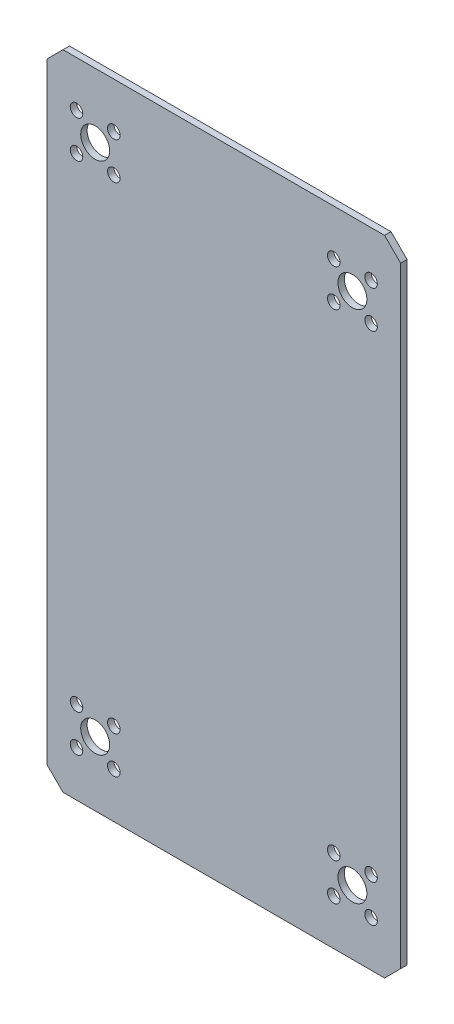
SolidWorks part; units mm, degrees
material "201 Annealed Stainless Steel (SS)"
ref_plane "Front Plane" through (0, 0, 0) normal (0, 0, 1) x (1, 0, 0)
ref_plane "Top Plane" through (0, 0, 0) normal (0, 1, 0) x (1, 0, 0)
ref_plane "Right Plane" through (0, 0, 0) normal (1, 0, 0) x (0, 0, -1)
sketch "Sketch1" plane through (0, 0, 0) normal (0, 0, 1) x (1, 0, 0)
  line L1 (-55, -100) -> (55, -100)
  line L2 (-55, -100) -> (-55, 100)
  line L3 (-55, 100) -> (55, 100)
  line L4 (55, -100) -> (55, 100)
  line L5 (-55, -100) -> (55, 100) construction
  line L6 (-55, 100) -> (55, -100) construction
  point P0 (0, 0)
  dimension "D1" = 110
  dimension "D2" = 200
extrude "Boss-Extrude1" add sketch "Sketch1" along normal blind 2
sketch "Sketch2" [suppressed] plane through (0, 0, 0) normal (0, 0, -1) x (-1, 0, 0)
  line L0 (61, 200) -> (61, -200) construction
  line L1 (-61, 314.7216) -> (-204.3993, 314.7216)
  line L2 (-61, 314.7216) -> (-61, -251.9618)
  line L3 (-61, -251.9618) -> (-204.3993, -251.9618)
  line L4 (-204.3993, 314.7216) -> (-204.3993, -251.9618)
  line L6 (61, 279.3211) -> (244.4765, 279.3211)
  line L7 (61, 279.3211) -> (61, -295.1839)
  line L8 (61, -295.1839) -> (244.4765, -295.1839)
  line L9 (244.4765, 279.3211) -> (244.4765, -295.1839)
  line L10 (-61, -200) -> (-61, -140) construction
extrude "Cut-Extrude1" [suppressed] cut sketch "Sketch2" against normal through all
sketch "Sketch3" [suppressed] plane through (49, 0, 0) normal (1, 0, 0) x (0, 0, -1)
  circle A0 centre (-6.722, 55.3681) radius 5.3835
surface "Surface-Extrude1" [suppressed] sketch "Sketch3"
sketch "Sketch4" [suppressed] plane through (-49, 0, 0) normal (-1, 0, 0) x (0, 0, 1)
  line L1 (2, 80) -> (0, 80) construction
  line L2 (0, -80) -> (0, 80) construction
  point P0 (7.5, 76)
  dimension "D1" = 4
  dimension "D2" = 7.5
ref_axis "Axis1" [suppressed] through (-49, 76, 7.5) along (1, 0, 0)
sketch "Sketch5" [suppressed] plane through (0, 0, 0) normal (0, 0, -1) x (-1, 0, 0)
  line L0 (49, 80) -> (49, -80) construction
  line L1 (-49, 80) -> (49, 80)
  line L2 (-49, 80) -> (-49, 60.2594)
  line L3 (-49, 60.2594) -> (49, 60.2594)
  line L4 (49, 80) -> (49, 60.2594)
extrude "Cut-Extrude2" [suppressed] cut sketch "Sketch5" against normal blind 3
sketch "Sketch6" plane through (0, 0, 2) normal (0, 0, 1) x (1, 0, 0)
  line L0 (0, 0) -> (103.2002, 0) construction
  line L1 (-40, 80) -> (-40, 108.3319) construction
  line L2 (-40, 80) -> (-27.987, 80) construction
  line L3 (0, 0) -> (0, 138.3235) construction
  line L4 (40, 80) -> (27.987, 80) construction
  line L5 (40, 80) -> (40, 108.3319) construction
  line L6 (40, -80) -> (40, -108.3319) construction
  line L7 (40, -80) -> (27.987, -80) construction
  line L8 (-40, -80) -> (-27.987, -80) construction
  line L9 (-40, -80) -> (-40, -108.3319) construction
  circle A0 centre (-40, 80) radius 4.5
  circle A2 centre (-45.8, 85.8) radius 1.95
  circle A3 centre (-45.8, 74.2) radius 1.95
  circle A4 centre (-34.2, 74.2) radius 1.95
  circle A5 centre (-34.2, 85.8) radius 1.95
  circle A6 centre (34.2, 85.8) radius 1.95
  circle A7 centre (34.2, 74.2) radius 1.95
  circle A8 centre (45.8, 74.2) radius 1.95
  circle A9 centre (45.8, 85.8) radius 1.95
  circle A10 centre (40, 80) radius 4.5
  circle A11 centre (40, -80) radius 4.5
  circle A12 centre (45.8, -85.8) radius 1.95
  circle A13 centre (45.8, -74.2) radius 1.95
  circle A14 centre (34.2, -74.2) radius 1.95
  circle A15 centre (34.2, -85.8) radius 1.95
  circle A16 centre (-34.2, -85.8) radius 1.95
  circle A17 centre (-34.2, -74.2) radius 1.95
  circle A18 centre (-45.8, -74.2) radius 1.95
  circle A19 centre (-45.8, -85.8) radius 1.95
  circle A20 centre (-40, -80) radius 4.5
  circle A21 centre (-40, 80) radius 5.1 construction
  point P52 (47.4466, 77.7566)
  point P53 (0, 0)
  point P54 (48.5598, 78.7073)
  dimension "D1" = 9
  dimension "D3" = 3.9
extrude "Leandut_holes" cut sketch "Sketch6" against normal through all
chamfer "Chamfer1" distance 5 angle 45 4 edges at (-55, -100, 1) (55, -100, 1) (55, 100, 1) (-55, 100, 1)
